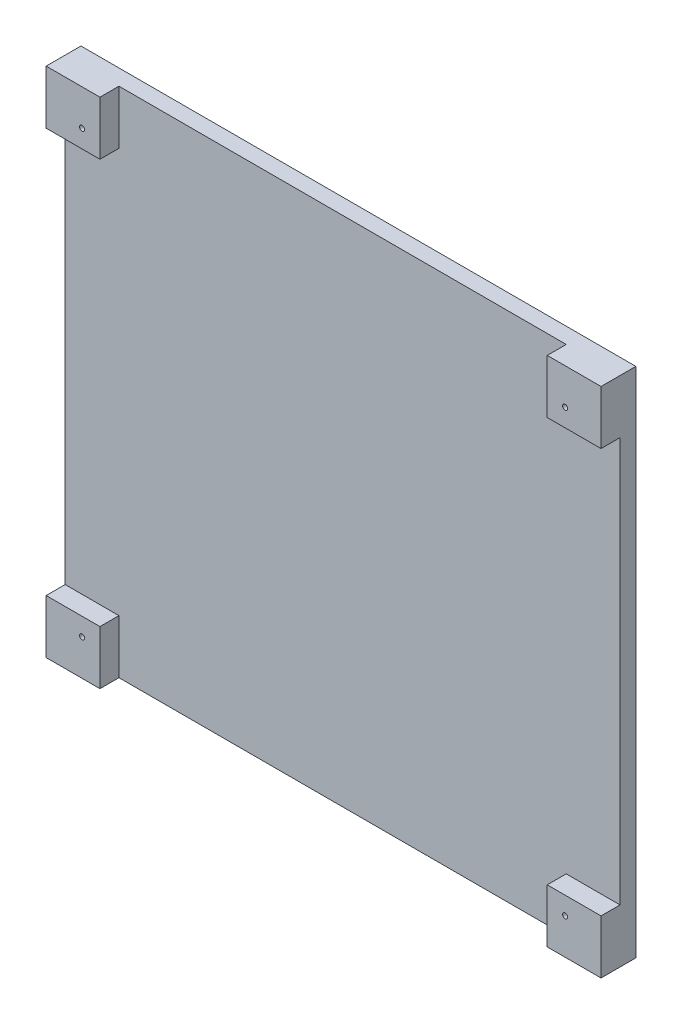
SolidWorks part; units mm, degrees
ref_plane "Front Plane" through (0, 0, 0) normal (1, 0, 0) x (0, 1, 0)
ref_plane "Top Plane" through (0, 0, 0) normal (0, 0, 1) x (0, 1, 0)
ref_plane "Right Plane" through (0, 0, 0) normal (0, 1, 0) x (-1, 0, 0)
sketch "Sketch1" plane through (0, 0, 0) normal (0, 0, 1) x (0, 1, 0)
  line L0 (-75.946, 82.677) -> (-80.946, 82.677) construction
  line L1 (-75.946, 82.677) -> (75.946, 82.677) construction
  line L2 (-75.946, 82.677) -> (-75.946, -82.677) construction
  line L3 (-75.946, -82.677) -> (75.946, -82.677) construction
  line L4 (75.946, 82.677) -> (75.946, -82.677) construction
  line L5 (-75.946, 82.677) -> (75.946, -82.677) construction
  line L6 (-75.946, -82.677) -> (75.946, 82.677) construction
  line L7 (-80.946, 87.677) -> (80.946, 87.677)
  line L8 (-80.946, 87.677) -> (-80.946, -87.677)
  line L9 (-80.946, -87.677) -> (80.946, -87.677)
  line L10 (80.946, 87.677) -> (80.946, -87.677)
  line L11 (-80.946, 87.677) -> (80.946, -87.677) construction
  line L12 (-80.946, -87.677) -> (80.946, 87.677) construction
  line L13 (-75.946, 82.677) -> (-75.946, 87.677) construction
  point P0 (0, 0)
  point P6 (0, 0)
  dimension "D1" = 151.892
  dimension "D2" = 165.354
  dimension "D3" = 5
extrude "Boss-Extrude1" add sketch "Sketch1" along normal blind 5
sketch "Sketch2" plane through (0, 0, 5) normal (0, 0, 1) x (1, 0, 0)
  line L1 (87.677, 80.946) -> (70.677, 80.946)
  line L2 (87.677, 80.946) -> (87.677, 63.946)
  line L3 (87.677, 63.946) -> (70.677, 63.946)
  line L4 (70.677, 80.946) -> (70.677, 63.946)
  line L5 (87.677, -80.946) -> (70.677, -80.946)
  line L6 (87.677, -80.946) -> (87.677, -63.946)
  line L7 (87.677, -63.946) -> (70.677, -63.946)
  line L8 (70.677, -80.946) -> (70.677, -63.946)
  line L9 (-87.677, -80.946) -> (-70.677, -80.946)
  line L10 (-87.677, -80.946) -> (-87.677, -63.946)
  line L11 (-87.677, -63.946) -> (-70.677, -63.946)
  line L12 (-70.677, -80.946) -> (-70.677, -63.946)
  line L13 (-87.677, 80.946) -> (-70.677, 80.946)
  line L14 (-87.677, 80.946) -> (-87.677, 63.946)
  line L15 (-87.677, 63.946) -> (-70.677, 63.946)
  line L16 (-70.677, 80.946) -> (-70.677, 63.946)
  line M3 (87.677, 80.946) -> (-87.677, 80.946)
  line M4 (-87.677, 80.946) -> (-87.677, -80.946)
  line M5 (-87.677, -80.946) -> (87.677, -80.946)
  line M6 (87.677, -80.946) -> (87.677, 80.946)
  dimension "D1" = 17
extrude "Boss-Extrude2" add sketch "Sketch2" along normal blind 6 contours L12 L11 M5 M4 | L8 L7 M5 M6 | L4 L3 M3 M6 | L16 L15 M3 M4 region at (79.177, 72.446, 5) region at (-79.177, 72.446, 5) region at (79.177, -72.446, 5) region at (-79.177, -72.446, 5)
sketch "Sketch3" plane through (0, 0, 11) normal (0, 0, 1) x (1, 0, 0)
  line L0 (-87.677, 80.946) -> (-87.677, 63.946) construction
  line L1 (-70.677, 80.946) -> (-87.677, 80.946) construction
  line L2 (0, 0) -> (0, -50000) construction
  line L3 (0, 0) -> (50000, 0) construction
  circle A0 centre (-76.327, 69.596) radius 0.8
  circle A1 centre (-76.327, -69.596) radius 0.8
  circle A2 centre (76.327, -69.596) radius 0.8
  circle A3 centre (76.327, 69.596) radius 0.8
  dimension "D3" = 1.6
  dimension "D1" = 11.35
  dimension "D2" = 11.35
extrude "Cut-Extrude1" cut sketch "Sketch3" against normal through all contours A0 | A3 | A2 | A1 region at (-76.327, 69.596, 11) region at (-76.327, -69.596, 11) region at (76.327, -69.596, 11) region at (76.327, 69.596, 11)
